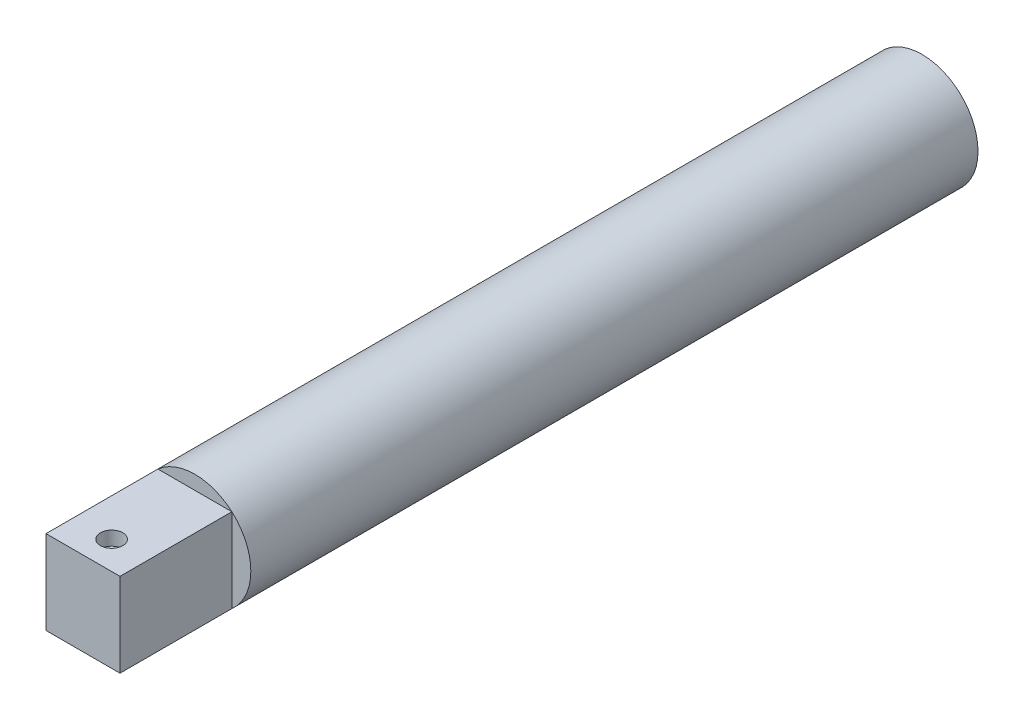
SolidWorks part; units mm, degrees
ref_plane "Front Plane" through (0, 0, 0) normal (0, 0, 1) x (1, 0, 0)
ref_plane "Top Plane" through (0, 0, 0) normal (0, 1, 0) x (1, 0, 0)
ref_plane "Right Plane" through (0, 0, 0) normal (1, 0, 0) x (0, 0, -1)
sketch "Sketch1" plane through (0, 0, 0) normal (0, 0, 1) x (1, 0, 0)
  circle A0 centre (0, 0) radius 10
  dimension "D1" = 20
extrude "Boss-Extrude1" add sketch "Sketch1" along normal blind 150
sketch "Sketch2" plane through (0, 0, 150) normal (0, 0, 1) x (1, 0, 0)
  line L1 (-6.6144, 7.5) -> (6.6144, 7.5)
  line L2 (-6.6144, 7.5) -> (-6.6144, -7.5)
  line L3 (-6.6144, -7.5) -> (6.6144, -7.5)
  line L4 (6.6144, 7.5) -> (6.6144, -7.5)
  circle A0 centre (0, 0) radius 10 construction
  circle A1 centre (0, 0) radius 10
  point P0 (0, 0)
  point P10 (0, 0)
  point P11 (0, 0)
  point P12 (0, 0)
  circle M3 centre (0, 0) radius 10
  dimension "D1" = 15
extrude "Cut-Extrude1" cut sketch "Sketch2" against normal blind 20 contours L1 M3 | L4 M3 | L3 M3 | L2 M3 region at (0, 8.5116, 150) region at (-7.9904, 0, 150) region at (7.9904, 0, 150) region at (0, -8.5116, 150)
sketch "Sketch3" plane through (0, 7.5, 0) normal (0, 1, 0) x (1, 0, 0)
  line L0 (6.6144, -130) -> (6.6144, -150) construction
  line L1 (-6.6144, -150) -> (6.6144, -150) construction
  circle A0 centre (0.1144, -145) radius 2
  circle A1 centre (0.1144, -145) radius 1
  dimension "D3" = 4
  dimension "D4" = 2
  dimension "D1" = 6.5
  dimension "D2" = 5
extrude "Cut-Extrude2" cut sketch "Sketch3" against normal blind 2.5
extrude "Cut-Extrude4" cut sketch "Sketch3<3>" along direction (0, -1, 0) on the side against the normal through all contours A1 region at (0.1144, 7.5, 145)
sketch "Sketch3<3>" plane through (0, 7.5, 0) normal (0, 1, 0) x (1, 0, 0) same geometry as "Sketch3"
sketch "Sketch7" plane through (0, 0, 0) normal (0, 0, -1) x (-1, 0, 0)
  circle A0 centre (5, 0) radius 1
  circle A1 centre (-5, 0) radius 1
  point P4 (0, 0)
  point P6 (0, 0)
  point P7 (3.0461, 0.0244)
  point P9 (0, 0)
  point P10 (0, 0)
  dimension "D1" = 2
  dimension "D2" = 2
  dimension "D3" = 10
  dimension "D4" = 5
extrude "Cut-Extrude5" cut sketch "Sketch7" against normal blind 10
